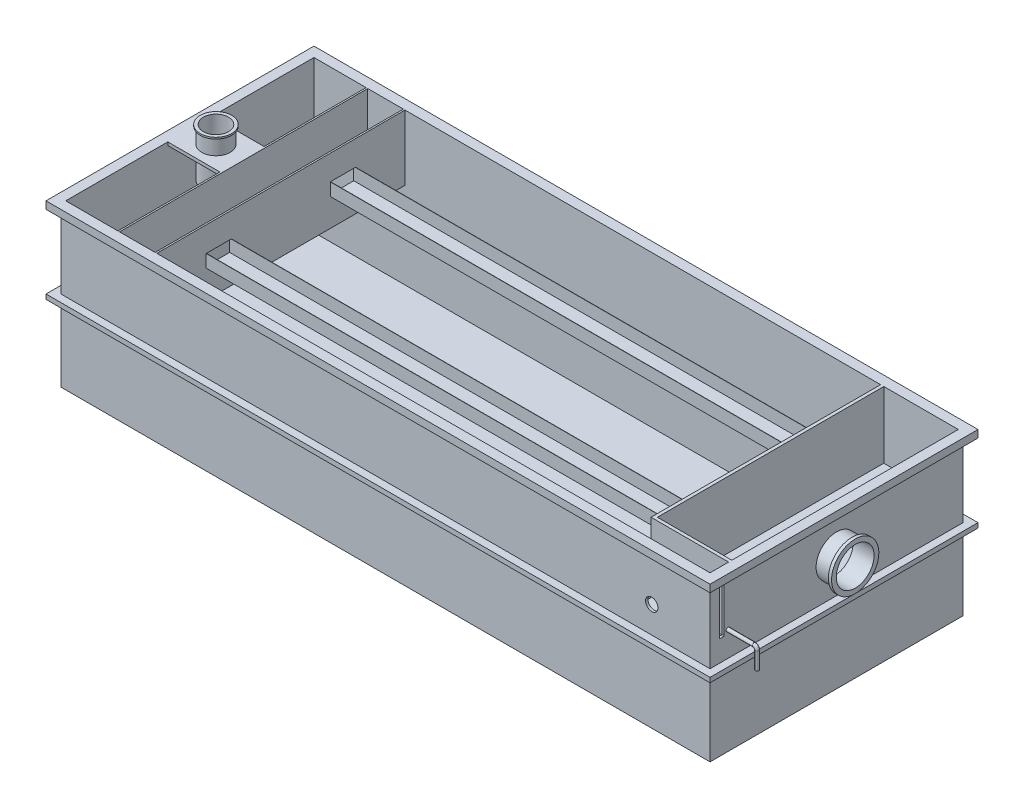
SolidWorks part; units mm, degrees
ref_plane "Plano frontal" through (0, 0, 0) normal (0, 0, 1) x (1, 0, 0)
ref_plane "Plano superior" through (0, 0, 0) normal (0, 1, 0) x (1, 0, 0)
ref_plane "Plano direito" through (0, 0, 0) normal (1, 0, 0) x (0, 0, -1)
sketch "Esboço1" plane through (0, 0, 0) normal (0, 1, 0) x (1, 0, 0)
  line L1 (-2675, -1079.5) -> (2675, -1079.5)
  line L2 (-2675, -1079.5) -> (-2675, 1079.5)
  line L3 (-2675, 1079.5) -> (2675, 1079.5)
  line L4 (2675, -1079.5) -> (2675, 1079.5)
  line L5 (-2675, -1079.5) -> (2675, 1079.5) construction
  line L6 (-2675, 1079.5) -> (2675, -1079.5) construction
  point P0 (0, 0)
extrude "Ressalto-extrusão1" add sketch "Esboço1" along normal blind 1300
sketch "Esboço2" plane through (0, 1300, 0) normal (0, 1, 0) x (1, 0, 0)
  line L1 (2595.5, -1000) -> (-2595.5, -1000)
  line L2 (2595.5, -1000) -> (2595.5, 1000)
  line L3 (2595.5, 1000) -> (-2595.5, 1000)
  line L4 (-2595.5, -1000) -> (-2595.5, 1000)
  line L5 (2595.5, -1000) -> (-2595.5, 1000) construction
  line L6 (2595.5, 1000) -> (-2595.5, -1000) construction
  point P0 (0, 0)
extrude "Corte-extrusão1" cut sketch "Esboço2" against normal blind 1220.5
sketch "Esboço3" plane through (0, 0, 1079.5) normal (0, 0, 1) x (1, 0, 0)
  line L0 (-2675, 1300) -> (-1875, 1300)
  line L3 (-2595.5, 79.5) -> (-2577.2813, 79.5)
  line L9 (-2675, 1300) -> (2675, 1300) construction
  line L10 (-1875, 1300) -> (-1875, 780)
  line L11 (-1875, 780) -> (-2595.5, 79.5)
  line L12 (-1862.3, 1300) -> (-1862.3, 774.6345)
  line L13 (-1862.3, 774.6345) -> (-2577.2813, 79.5)
  line L14 (-1862.3, 774.6345) -> (-2586.647, 70.3943) construction
  line L15 (-1875, 1300) -> (-1862.3, 1300)
  line M5 (2675, 1300) -> (-2675, 1300)
  dimension "D1" = 12.7
extrude "Ressalto-extrusão6" add sketch "Esboço3" against normal up to surface (2079.5 mm away) contours L3 M5 region at (-2234.2575, 428.7292, 1079.5) up to face at (0, 689.75, -1000)
sketch "Esboço4" plane through (0, 0, 0) normal (0, -1, 0) x (1, 0, 0)
  line L5 (-2675, 1079.5) -> (2675, 1079.5)
  line L6 (-2675, 1079.5) -> (-2675, -1079.5)
  line L7 (-2675, -1079.5) -> (2675, -1079.5)
  line L8 (2615, -1019.5) -> (2615, 1019.5)
  line L9 (2615, 1019.5) -> (-2615, 1019.5)
  line L10 (-2615, 1019.5) -> (-2615, -1019.5)
  line L11 (-2615, -1019.5) -> (2615, -1019.5)
  line L12 (2615, -1019.5) -> (2615, 1019.5)
  line L13 (2615, 1019.5) -> (-2615, 1019.5)
  line L14 (-2615, 1019.5) -> (-2615, -1019.5)
  line L15 (-2615, -1019.5) -> (2615, -1019.5)
  line L16 (2675, 1079.5) -> (2675, -1079.5)
  dimension "D1" = 60
extrude "Corte-extrusão2" cut sketch "Esboço4" against normal blind 1240
sketch "Esboço8" plane through (2615, 0, 0) normal (1, 0, 0) x (0, 0, -1)
  line L0 (0, 0) -> (0, 930)
  line L1 (1019.5, 0) -> (-1019.5, 0) construction
  circle A0 centre (0, 930) radius 152.4
  circle A1 centre (0, 930) radius 165.1
extrude "Corte-extrusão3" cut sketch "Esboço8" against normal up to surface (19.5 mm away) contours A0 up to face at (2595.5, 689.75, 0)
extrude "Ressalto-extrusão7" add sketch "Esboço8<3>" along normal blind 124.6 contours A1 A0 region at (2615, 1043.4413, 113.4413)
sketch "Esboço8<3>" plane through (2615, 0, 0) normal (1, 0, 0) x (0, 0, -1) same geometry as "Esboço8"
sketch "Esboço10" plane through (2739.6, 0, 0) normal (1, 0, 0) x (0, 0, -1)
  circle A0 centre (0, 930) radius 190.5
  circle A1 centre (0, 930) radius 152.4
extrude "Ressalto-extrusão8" add sketch "Esboço10" along normal blind 25.4
sketch "Esboço12" plane through (0, 1300, 0) normal (0, 1, 0) x (1, 0, 0)
  line L0 (2595.5, 1000) -> (1995.5, 1000)
  line L1 (2595.5, 1000) -> (-1862.3, 1000) construction
  line L2 (1995.5, 1000) -> (1995.5, -824.6)
  line L3 (1995.5, -824.6) -> (2595.5, -824.6)
  line L4 (2595.5, -1000) -> (2595.5, 1000) construction
  line L5 (1970.1, 1000) -> (1970.1, -850)
  line L7 (1970.1, -850) -> (2595.5, -850)
  line L8 (2595.5, -824.6) -> (2595.5, -850)
  line L9 (1995.5, 1000) -> (1970.1, 1000)
  line L11 (1970.1, 1000) -> (2595.5, 1000)
  line L12 (1970.1, 1000) -> (1970.1, -850)
  line L13 (1970.1, -850) -> (2595.5, -850)
  line L14 (2595.5, 1000) -> (2595.5, -850)
  line M15 (-1862.3, 1000) -> (2595.5, 1000)
  line M16 (2595.5, 1000) -> (2595.5, -1000)
  dimension "D1" = 25.4
extrude "Ressalto-extrusão10" add sketch "Esboço12" against normal blind 560.8 contours L5 L7 L3 L2 M16 M15 | L2 L3 M16 M15 region at (2295.5, 1300, -87.7) region at (1975.9715, 1300, -87.7)
extrude "Corte-extrusão4" cut sketch "Esboço12<4>" against normal blind 535.4 contours L2 L3 M16 M15 region at (2295.5, 1300, -87.7)
sketch "Esboço12<4>" plane through (0, 1300, 0) normal (0, 1, 0) x (1, 0, 0) same geometry as "Esboço12"
sketch "Esboço16" plane through (0, 1300, 0) normal (0, 1, 0) x (1, 0, 0)
  line L0 (-2675, 1079.5) -> (-2675, -1079.5) construction
  line L1 (-2675, 0) -> (-2175, 0)
  line L2 (-2675, -177.8) -> (-2675, 177.8)
  line L3 (-2675, 177.8) -> (-2175, 177.8)
  line L4 (-2175, -177.8) -> (-2175, 177.8)
  line L6 (-2675, -177.8) -> (-2175, -177.8)
  line L7 (-1875, 1000) -> (-2595.5, 1000) construction
  line L8 (-2175, 0) -> (-2162.3, 0)
  line L9 (-2175, -1000) -> (-2175, 1000)
  line L10 (-2175, 1000) -> (-2162.3, 1000)
  line L11 (-2162.3, -1000) -> (-2162.3, 1000)
  line L12 (-2175, -1000) -> (-2162.3, -1000)
  line M18 (-1875, -1000) -> (-2595.5, -1000)
  line M19 (-2595.5, -1000) -> (-2595.5, 1000)
  line M20 (-2595.5, 1000) -> (-1875, 1000)
extrude "Ressalto-extrusão11" add sketch "Esboço16" against normal blind 25.4 contours L1 L4 L3 M19 | L6 L4 L1 M19 region at (-2385.25, 1300, -88.9) region at (-2385.25, 1300, 88.9)
extrude "Ressalto-extrusão12" add sketch "Esboço16<3>" against normal blind 400 contours L8 L11 L9 L4 M20 | L11 L8 L4 L9 M18 region at (-2168.65, 1300, 500) region at (-2168.65, 1300, -500)
sketch "Esboço16<3>" plane through (0, 1300, 0) normal (0, 1, 0) x (1, 0, 0) same geometry as "Esboço16"
sketch "Esboço17" plane through (0, 1300, 0) normal (0, 1, 0) x (1, 0, 0)
  circle A0 centre (-2385.25, 0) radius 114.3
extrude "Ressalto-extrusão13" add sketch "Esboço17" along normal blind 125.5 and the other way blind 250
sketch "Esboço18" plane through (0, 1425.5, 0) normal (0, 1, 0) x (1, 0, 0)
  circle A0 centre (-2385.25, 0) radius 127
extrude "Ressalto-extrusão14" add sketch "Esboço18" along normal blind 12.7
sketch "Esboço19" plane through (0, 1438.2, 0) normal (0, 1, 0) x (1, 0, 0)
  circle A0 centre (-2385.25, 0) radius 101.6
extrude "Corte-extrusão6" cut sketch "Esboço19" against normal up to next contours A0
sketch "Esboço20" plane through (-1862.3, 0, 0) normal (1, 0, 0) x (0, 0, -1)
  line L0 (0, 1300) -> (-1000, 1300)
  line L1 (-1079.5, 1300) -> (1079.5, 1300) construction
  line L2 (-500, 1300) -> (-500, 1100)
  line L3 (-600, 1100) -> (-600, 1000)
  line L4 (-600, 1100) -> (-400, 1100)
  line L5 (-500, 1100) -> (-500, 1000)
  line L6 (-600, 1000) -> (-400, 1000)
  line L7 (-400, 1100) -> (-400, 1000)
  line L8 (0, 1300) -> (0, 900)
  line L9 (-1000, 900) -> (1000, 900) construction
  line L10 (400, 1100) -> (400, 1000)
  line L11 (600, 1000) -> (400, 1000)
  line L12 (600, 1100) -> (400, 1100)
  line L13 (600, 1100) -> (600, 1000)
extrude "Corte-extrusão7" cut sketch "Esboço20" against normal up to next contours L7 L4 L5 L6 | L3 L6 L5 L4 | L13 L12 L10 L11 region at (-1862.3, 1050, 550) region at (-1862.3, 1050, 450) region at (-1862.3, 1050, -500)
sketch "Esboço21" plane through (-1862.3, 0, 0) normal (1, 0, 0) x (0, 0, -1)
  line L16 (-606.35, 1100) -> (606.35, 1100)
  line L17 (-602, 1102) -> (-602, 998)
  line L18 (-600, 1100) -> (-400, 1100)
  line L19 (-600, 1100) -> (-600, 1000)
  line L20 (-600, 1000) -> (-400, 1000)
  line L21 (-400, 1100) -> (-400, 1000)
  line L22 (-602, 998) -> (-398, 998)
  line L23 (-398, 1102) -> (-398, 998)
  line L24 (-602, 1102) -> (-398, 1102)
  line L25 (0, 1100) -> (0, 1036.475)
  line L26 (602, 1102) -> (398, 1102)
  line L27 (398, 1102) -> (398, 998)
  line L28 (602, 998) -> (398, 998)
  line L29 (400, 1100) -> (400, 1000)
  line L30 (600, 1000) -> (400, 1000)
  line L31 (600, 1100) -> (600, 1000)
  line L32 (600, 1100) -> (400, 1100)
  line L33 (602, 1102) -> (602, 998)
  line M9 (600, 1100) -> (600, 1000)
  line M10 (600, 1000) -> (400, 1000)
  line M11 (400, 1000) -> (400, 1100)
  line M17 (-400, 1100) -> (-400, 1000)
  line M18 (-400, 1000) -> (-600, 1000)
  line M19 (-600, 1000) -> (-600, 1100)
  dimension "D1" = 2
extrude "Ressalto-extrusão15" add sketch "Esboço21" along normal up to surface (3832.4 mm away) contours L23 L16 L17 L22 M17 M18 M19 | L33 L16 L27 L28 M9 M10 M11 region at (-1862.3, 1050, 600.2281) region at (-1862.3, 1097.7192, -399) up to face at (1970.1, 1019.6, -75)
sketch "Esboço24" plane through (0, 764.6, 0) normal (0, 1, 0) x (1, 0, 0)
  circle A0 centre (2295.5, 0) radius 120
extrude "Corte-extrusão8" cut sketch "Esboço24" against normal up to next
sketch "Esboço23" plane through (0, 0, 1019.5) normal (0, 0, 1) x (1, 0, 0)
  line L0 (1970.1, 739.2) -> (1970.1, 1300) construction
  line L7 (1970.1, 764.6) -> (2595.5, 764.6)
  line L8 (1970.1, 764.6) -> (1970.1, 739.2)
  line L9 (1970.1, 739.2) -> (2595.5, 739.2)
  line L10 (2595.5, 764.6) -> (2595.5, 739.2)
  line L11 (1995.5, 764.6) -> (1995.5, 1300) construction
  line L16 (1970.1, 764.6) -> (1995.5, 764.6)
  line L17 (1970.1, 764.6) -> (1970.1, 840)
  line L18 (1970.1, 840) -> (1995.5, 840)
  line L19 (1995.5, 764.6) -> (1995.5, 840)
extrude "Ressalto-extrusão16" add sketch "Esboço23" against normal up to surface (169.5 mm away) contours L7 L19 L18 L17 | L9 L10 L7 L8 region at (1982.8, 802.3, 1019.5) up to face at (2282.8, 1019.6, 850)
sketch "Esboço32" plane through (0, 0, 1019.5) normal (0, 0, 1) x (1, 0, 0)
  line L0 (1970.1, 840) -> (1295.5, 179.5)
  line L1 (2595.5, 79.5) -> (2595.5, 179.5)
  line L2 (2595.5, 79.5) -> (2595.5, 739.2) construction
  line L3 (2595.5, 179.5) -> (1295.5, 179.5)
  line L4 (1970.1, 831.1131) -> (1311.0622, 185.85)
  line L5 (1311.0622, 185.85) -> (1304.5766, 179.5)
  line L6 (2601.85, 79.5) -> (2601.85, 185.85)
  line L7 (1970.1, 840) -> (1970.1, 831.1131)
  line L8 (2601.85, 185.85) -> (1311.0622, 185.85) construction
  line L10 (1974.5425, 835.4627) -> (1311.0622, 185.85) construction
  dimension "D1" = 6.35
extrude "Ressalto-extrusão20" add sketch "Esboço32" against normal up to surface (2019.5 mm away) contours L7 L0 L3 L5 L4 region at (1635.064, 507.5333, 1019.5) up to face at (404.1884, 716.0049, -1000)
ref_plane "Plano1" through (0, 650, 0) normal (0, 1, 0) x (1, 0, 0)
sketch "Esboço33" plane through (0, 650, 0) normal (0, 1, 0) x (1, 0, 0)
  line L1 (-2675, 1079.5) -> (2675, 1079.5)
  line L2 (-2675, 1079.5) -> (-2675, -1079.5)
  line L3 (-2675, -1079.5) -> (2675, -1079.5)
  line L4 (2675, 1079.5) -> (2675, -1079.5)
  line L5 (-2615, 1019.5) -> (2615, 1019.5)
  line L6 (-2615, 1019.5) -> (-2615, -1019.5)
  line L7 (-2615, -1019.5) -> (2615, -1019.5)
  line L8 (2615, 1019.5) -> (2615, -1019.5)
extrude "Ressalto-extrusão21" add sketch "Esboço33" against normal blind 38.1
sketch "Esboço34" plane through (2615, 0, 0) normal (1, 0, 0) x (0, 0, -1)
  line L0 (-850, 764.6) -> (-1000, 764.6)
  line L2 (-925, 764.6) -> (-925, 901.9)
  circle A0 centre (-925, 901.9) radius 15
  circle A1 centre (-925, 901.9) radius 12.7
extrude "Ressalto-extrusão22" add sketch "Esboço34" against normal blind 280 contours A0 region at (2615, 912.2066, 935.3066)
sketch "Esboço35" plane through (2335, 0, 0) normal (-1, 0, 0) x (0, 0, 1)
  line L0 (925, 915.9776) -> (925, 925.9776)
  line L1 (925, 925.9776) -> (945, 925.9776)
  circle A0 centre (925, 901.9) radius 14.0776
  circle A1 centre (925, 901.9) radius 12.7
revolve "Revolução1" add sketch "Esboço35" angle 90 about L1 region at (2335, 892.2272, 915.3272) reverse direction yes
sketch "Esboço36" plane through (0, 925.9776, 0) normal (0, 1, 0) x (1, 0, 0)
  circle A0 centre (2310.9224, -925) radius 14.0776
  circle A1 centre (2310.9224, -925) radius 12.7
extrude "Ressalto-extrusão23" add sketch "Esboço36" along normal blind 140
ref_plane "Plano3" through (2605.25, 0, 0) normal (1, 0, 0) x (0, 0, -1)
sketch "Esboço37" plane through (2605.25, 0, 0) normal (1, 0, 0) x (0, 0, -1)
  line L0 (-940, 901.9) -> (-910, 901.9)
  circle A0 centre (-925, 901.9) radius 15 construction
pattern_circular "PadrãoCircular1" count 2 every 180 about axis through (2605.25, 901.9, 940) along (0, 0, -1) of "Ressalto-extrusão23", "Ressalto-extrusão22", "Revolução1" reverse direction yes
sketch "Esboço38" plane through (0, 0, 1019.5) normal (0, 0, 1) x (1, 0, 0)
  line L0 (2595.5, 764.6) -> (2145.5, 764.6)
  line L1 (1995.5, 764.6) -> (2595.5, 764.6) construction
  line L2 (2145.5, 764.6) -> (2145.5, 864.6)
  circle A0 centre (2145.5, 864.6) radius 50
extrude "Corte-extrusão11" cut sketch "Esboço38" along direction (0, 0, 1) on the side against the normal up to next (19.5 mm away) contours A0 region at (2179.8553, 830.2447, 1019.5)
sketch "Sketch1" plane through (2615, 0, 0) normal (1, 0, 0) x (0, 0, -1)
  line L1 (-939.6, 1179.6) -> (-910.4, 1179.6)
  line L2 (-944.6, 1174.6) -> (-944.6, 825)
  line L3 (-939.6, 820) -> (-910.4, 820)
  line L4 (-905.4, 1174.6) -> (-905.4, 825)
  arc A0 (-944.6, 1174.6) -> (-939.6, 1179.6) centre (-939.6, 1174.6) cw
  arc A1 (-905.4, 1174.6) -> (-910.4, 1179.6) centre (-910.4, 1174.6) ccw
  arc A2 (-939.6, 820) -> (-944.6, 825) centre (-939.6, 825) cw
  arc A3 (-910.4, 820) -> (-905.4, 825) centre (-910.4, 825) ccw
  point P5 (0, 0)
  point P9 (-944.6, 1179.6)
  point P16 (-905.4, 820)
  point P17 (0, 0)
  point P18 (0, 0)
  point P19 (0, 0)
  point P20 (0, 0)
  point P22 (0, 0)
  point P23 (0, 0)
  dimension "D1" = 5
extrude "Cut-Extrude1" cut sketch "Sketch1" against normal blind 60 and the other way blind 50
